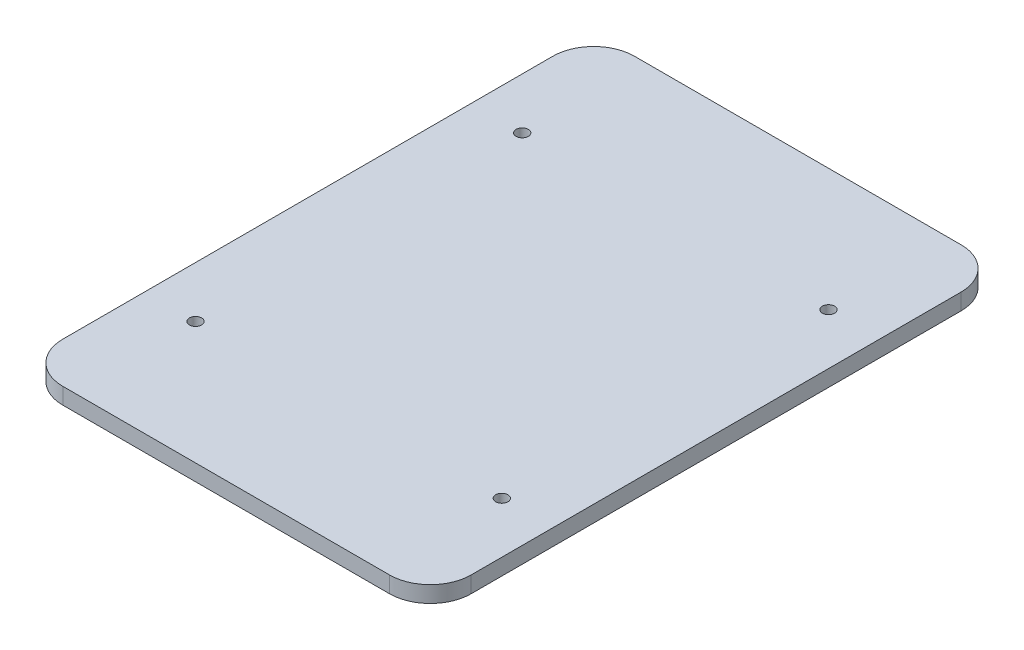
SolidWorks part; units mm, degrees
ref_plane "前视基准面" through (0, 0, 0) normal (0, 0, 1) x (1, 0, 0)
ref_plane "上视基准面" through (0, 0, 0) normal (0, 1, 0) x (1, 0, 0)
ref_plane "右视基准面" through (0, 0, 0) normal (1, 0, 0) x (0, 0, -1)
other "Configuration Table"
sketch "草图1" plane through (0, 0, 0) normal (0, 1, 0) x (1, 0, 0)
  line L0 (37.5, -40) -> (-37.5, -40) construction
  line L1 (-50, -70) -> (50, -70)
  line L2 (-50, -70) -> (-50, 70)
  line L3 (-50, 70) -> (50, 70)
  line L4 (50, -70) -> (50, 70)
  line L5 (-50, -70) -> (50, 70) construction
  line L6 (-50, 70) -> (50, -70) construction
  line L7 (37.5, -40) -> (37.5, 40) construction
  line L8 (37.5, 40) -> (-37.5, 40) construction
  line L9 (-37.5, -40) -> (-37.5, 40) construction
  line L10 (37.5, -40) -> (-37.5, 40) construction
  line L11 (37.5, 40) -> (-37.5, -40) construction
  circle A0 centre (-37.5, 40) radius 1.5
  circle A1 centre (37.5, 40) radius 1.5
  circle A2 centre (37.5, -40) radius 1.5
  circle A3 centre (-37.5, -40) radius 1.5
  point P0 (0, 0)
  point P6 (0, 0)
  point P15 (0, 0)
  dimension "D3" = 3
  dimension "D1" = 75
  dimension "D2" = 80
  dimension "D4" = 100
  dimension "D5" = 140
extrude "凸台-拉伸1" add sketch "草图1" along normal blind 4
fillet "圆角1" radius 10 4 edges at (-50, 2, -70) (50, 2, -70) (-50, 2, 70) (50, 2, 70)
